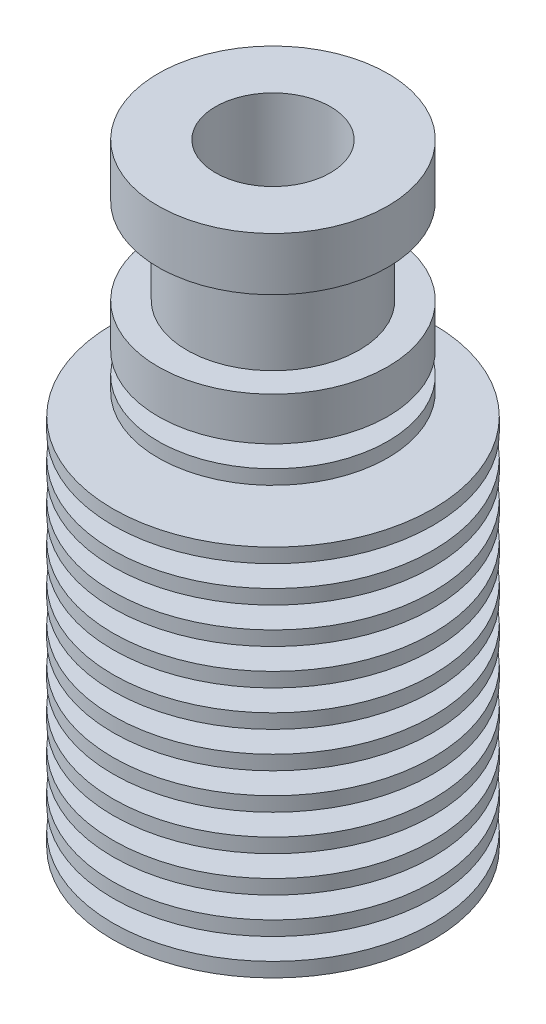
SolidWorks part; units mm, degrees
ref_plane "Front Plane" through (0, 0, 0) normal (0, 0, 1) x (1, 0, 0)
ref_plane "Top Plane" through (0, 0, 0) normal (0, 1, 0) x (1, 0, 0)
ref_plane "Right Plane" through (0, 0, 0) normal (1, 0, 0) x (0, 0, -1)
sketch "Sketch1" plane through (0, 0, 0) normal (0, 0, 1) x (1, 0, 0)
  line L0 (0, 0) -> (-8, 0)
  line L1 (-8, 0) -> (-8, -3.7)
  line L2 (-8, -3.7) -> (-6, -3.7)
  line L3 (-6, -3.7) -> (-6, -9.7)
  line L4 (-6, -9.7) -> (-8, -9.7)
  line L5 (-8, -9.7) -> (-8, -12.7)
  line L6 (-8, -12.7) -> (-4.5, -12.7)
  line L7 (-4.5, -12.7) -> (-4.5, -14.2)
  line L8 (-4.5, -14.2) -> (-8, -14.2)
  line L9 (-8, -14.2) -> (-8, -15.2)
  line L10 (-8, -15.2) -> (-4.6591, -15.2)
  line L11 (-4.6591, -15.2) -> (-4.6591, -16.7)
  line L12 (-4.6591, -16.7) -> (-11.15, -16.7)
  line L13 (-11.15, -16.7) -> (-11.15, -17.7)
  line L14 (-11.15, -17.7) -> (-4.8182, -17.7)
  line L15 (-4.8182, -17.7) -> (-4.8182, -19.2)
  line L16 (-4.8182, -19.2) -> (-11.15, -19.2)
  line L17 (-11.15, -19.2) -> (-11.15, -20.2)
  line L18 (-11.15, -20.2) -> (-4.9773, -20.2)
  line L19 (-4.9773, -20.2) -> (-4.9773, -21.7)
  line L20 (-4.9773, -21.7) -> (-11.15, -21.7)
  line L21 (-11.15, -21.7) -> (-11.15, -22.7)
  line L22 (-11.15, -22.7) -> (-5.1364, -22.7)
  line L23 (-5.1364, -22.7) -> (-5.1364, -24.2)
  line L24 (-5.1364, -24.2) -> (-11.15, -24.2)
  line L25 (-11.15, -24.2) -> (-11.15, -25.2)
  line L26 (-11.15, -25.2) -> (-5.2955, -25.2)
  line L27 (-5.2955, -25.2) -> (-5.2955, -26.7)
  line L28 (-5.2955, -26.7) -> (-11.15, -26.7)
  line L29 (-11.15, -26.7) -> (-11.15, -27.7)
  line L30 (-11.15, -27.7) -> (-5.4545, -27.7)
  line L31 (-5.4545, -27.7) -> (-5.4545, -29.2)
  line L32 (-5.4545, -29.2) -> (-11.15, -29.2)
  line L33 (-11.15, -29.2) -> (-11.15, -30.2)
  line L34 (-11.15, -30.2) -> (-5.6136, -30.2)
  line L35 (-5.6136, -30.2) -> (-5.6136, -31.7)
  line L36 (-5.6136, -31.7) -> (-11.15, -31.7)
  line L37 (-11.15, -31.7) -> (-11.15, -32.7)
  line L38 (-11.15, -32.7) -> (-5.7727, -32.7)
  line L39 (-5.7727, -32.7) -> (-5.7727, -34.2)
  line L40 (-5.7727, -34.2) -> (-11.15, -34.2)
  line L41 (-11.15, -34.2) -> (-11.15, -35.2)
  line L42 (-11.15, -35.2) -> (-5.9318, -35.2)
  line L43 (-5.9318, -35.2) -> (-5.9318, -36.7)
  line L44 (-5.9318, -36.7) -> (-11.15, -36.7)
  line L45 (-11.15, -36.7) -> (-11.15, -37.7)
  line L46 (-11.15, -37.7) -> (-6.0909, -37.7)
  line L47 (-6.0909, -37.7) -> (-6.0909, -39.2)
  line L48 (-6.0909, -39.2) -> (-11.15, -39.2)
  line L49 (-11.15, -39.2) -> (-11.15, -40.2)
  line L50 (-11.15, -40.2) -> (-6.25, -40.2)
  line L51 (-6.25, -40.2) -> (-6.25, -41.7)
  line L52 (-6.25, -41.7) -> (-11.15, -41.7)
  line L53 (-11.15, -41.7) -> (-11.15, -42.7)
  line L54 (-4.5, -12.7) -> (-6.25, -40.2) construction
  line L55 (-3.04, -42.7) -> (-3.04, -27.9)
  line L56 (-3.04, -27.9) -> (-2, -27.2996)
  line L57 (-2, -27.2996) -> (-2, -7.6547)
  line L58 (-2, -7.6547) -> (-4, -6.5)
  line L59 (-2, -27.2996) -> (-2, -42.7)
  line L61 (-11.15, -42.7) -> (0, -42.7)
  line L62 (-4, -6.5) -> (-4, 0)
  line L63 (0, -42.7) -> (0, 0)
  dimension "D1" = 42.7
  dimension "D2" = 6.25
  dimension "D3" = 4.5
  dimension "D4" = 8
  dimension "D5" = 4
  dimension "D6" = 2
  dimension "D7" = 11.15
  dimension "D8" = 14.8
  dimension "D9" = 60
  dimension "D10" = 3.7
  dimension "D11" = 6
  dimension "D12" = 3
  dimension "D13" = 1
  dimension "D14" = 2.5
  dimension "D15" = 3.04
  dimension "D16" = 60
  dimension "D17" = 6
  dimension "D18" = 6.5
revolve "Revolve1" add sketch "Sketch1" angle 360 about L63
hole_wizard "Tap Drill for M7x1.0 Tap3" positions "3DSketch5" profile "Sketch6" hole size "M7x1.0" standard "ANSI Metric"
sketch3d "3DSketch5"
  line L0 (0, -41.7, 0) -> (0, -42.7, 0) construction
  point P0 (0, -42.7, 0)
sketch "Sketch6" plane through (0, -42.7, 0) normal (1, 0, 0) x (0, 0, -1)
  line L0 (0, 0) -> (0, 10.5)
  line L1 (0, 10.5) -> (3, 10.5)
  line L2 (3, 10.5) -> (3, 0)
  line L5 (3, 0) -> (0, 0)
  line L10 (0, 10.5) -> (-3, 10.5) construction
  line L11 (0, -6.35) -> (0, 107.95) construction
  dimension "Hole Dia." = 6
  dimension "Hole Depth" = 10.5
  dimension "Drill Angle" = 180
revolve "Cut-Revolve1" cut sketch "Sketch1<4>" angle 360 about L63 region at (-1.2805, -18.8187, 0)
sketch "Sketch1<4>" plane through (0, 0, 0) normal (0, 0, 1) x (1, 0, 0) same geometry as "Sketch1"
